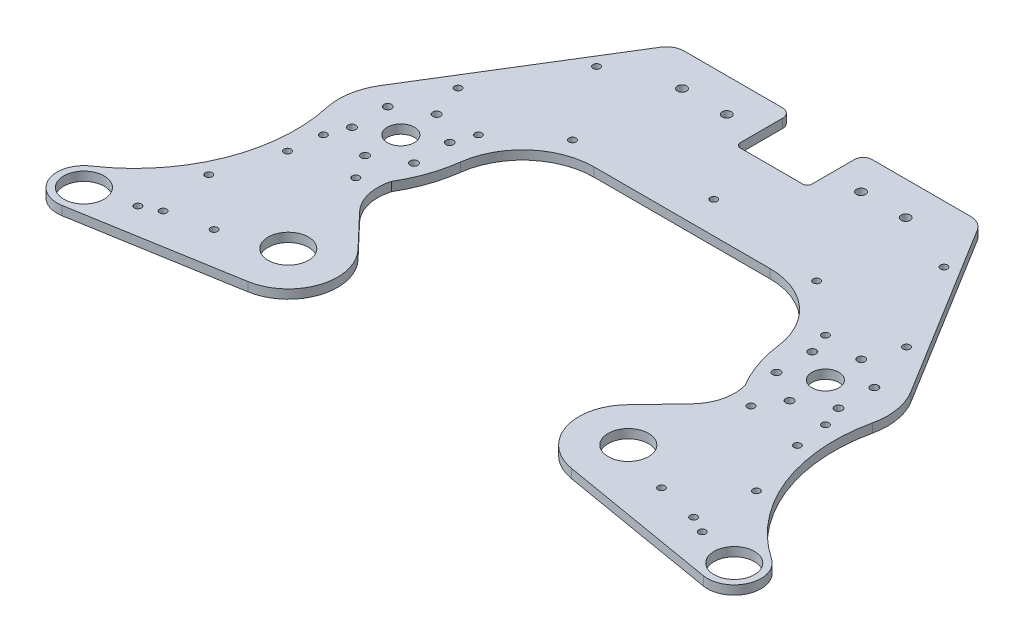
SolidWorks part; units mm, degrees
other "Marca1"
sketch "Croquis4" plane through (-508, 6.35, -221.5657) normal (0, 1, 0) x (1, 0, 0)
sketch "Croquis5" plane through (-262.5313, 6.35, -249.2375) normal (0, 1, 0) x (1, 0, 0)
sketch "Croquis6" plane through (-161.9393, 4.5, -121.1622) normal (0, 1, 0) x (1, 0, 0)
sketch "Croquis7" plane through (-262.5313, 6.35, -249.2375) normal (0, 1, 0) x (1, 0, 0)
sketch "Croquis9" plane through (-161.9393, 10.85, -121.1622) normal (0, 1, 0) x (1, 0, 0)
sketch "Croquis10" plane through (-262.5313, 6.35, -249.2375) normal (0, 1, 0) x (1, 0, 0)
sketch "Croquis12" plane through (-264.3199, 10.85, -20.8386) normal (0, 1, 0) x (1, 0, 0)
sketch "Croquis15" plane through (-262.5313, 6.35, -249.2375) normal (0, 1, 0) x (1, 0, 0)
sketch "Croquis16" plane through (-262.5313, 6.35, -249.2375) normal (0, 1, 0) x (1, 0, 0)
sketch "Croquis17" plane through (-262.5313, 6.35, -249.2375) normal (0, 1, 0) x (1, 0, 0)
sketch "Croquis18" plane through (-262.5313, 6.35, -249.2375) normal (0, 1, 0) x (1, 0, 0)
sketch "Croquis19" [suppressed] plane through (-264.3199, 10.85, -20.8386) normal (0, 1, 0) x (1, 0, 0)
sketch "Croquis20" [suppressed] plane through (-161.9393, 10.85, -121.1622) normal (0, 1, 0) x (1, 0, 0)
sketch "Croquis21" plane through (-264.3199, 10.85, -20.8386) normal (0, 1, 0) x (1, 0, 0)
sketch "Croquis22" plane through (-262.5313, 6.35, -249.2375) normal (0, 1, 0) x (1, 0, 0)
sketch "Croquis23" plane through (-262.5313, 6.35, -261.9375) normal (0, 1, 0) x (1, 0, 0)
sketch "Croquis24" plane through (-262.5313, 6.35, -261.9375) normal (0, 1, 0) x (1, 0, 0)
sketch "Croquis26" plane through (-262.5313, 7.9375, -34.9979) normal (0, 1, 0) x (1, 0, 0)
sketch "Croquis27" plane through (-262.5313, 6.35, -261.9375) normal (0, 1, 0) x (1, 0, 0)
sketch "Croquis28" plane through (-262.5313, 7.9375, -34.9979) normal (0, 1, 0) x (1, 0, 0)
sketch "Croquis29" plane through (-262.5313, 6.35, -261.9375) normal (0, 1, 0) x (1, 0, 0)
sketch "Croquis30" [suppressed] plane through (-262.5313, 7.9375, -34.9979) normal (0, 1, 0) x (1, 0, 0)
sketch "Croquis31" plane through (-262.5313, 7.9375, -34.9979) normal (0, 1, 0) x (1, 0, 0)
sketch "Croquis32" plane through (-161.9393, 10.85, -121.1622) normal (0, 1, 0) x (1, 0, 0)
material "Acrílico (Impacto medio-alto)"
ref_plane "Alzado" through (0, 0, 0) normal (0, 0, 1) x (1, 0, 0)
ref_plane "Planta" through (0, 0, 0) normal (0, 1, 0) x (1, 0, 0)
ref_plane "Vista lateral" through (0, 0, 0) normal (1, 0, 0) x (0, 0, -1)
sketch "Dibujo" plane through (0, 0, 0) normal (0, 1, 0) x (1, 0, 0)
  line L0 (0, 0) -> (0, 158.75) construction
  line L1 (0, 158.75) -> (-508, 158.75) construction
  line L2 (-126.4251, 18.2045) -> (-236.5182, -16.7205) construction
  line L3 (-224.9681, -53.1295) -> (-114.8749, -18.2045) construction
  line L4 (-160.1534, 108.938) -> (-149.1603, -2.8048) construction
  line L5 (-141.9901, 113.8973) -> (-94.6704, 12.0732) construction
  circle A0 centre (-120.65, 0) radius 50.8
  circle A1 centre (-230.7431, -34.925) radius 28.575
  arc A2 (-236.5182, -16.7205) -> (-224.9681, -53.1295) centre (-230.7431, -34.925) ccw construction
  arc A3 (-114.8749, -18.2045) -> (-126.4251, 18.2045) centre (-120.65, 0) ccw construction
  circle A4 centre (-150.65, 109.8729) radius 30
  arc A5 (-141.9901, 113.8973) -> (-160.1534, 108.938) centre (-150.65, 109.8729) ccw construction
  arc A6 (-149.1603, -2.8048) -> (-94.6704, 12.0732) centre (-120.65, 0) ccw construction
  dimension "D1" = 101.6
  dimension "D5" = 57.15
  dimension "D6" = 38.1972
  dimension "D9" = 60
  dimension "D10" = 19.0986
  dimension "D11" = 57.2958
  dimension "D2" = 241.3
  dimension "D3" = 508
  dimension "D4" = 107.95
  dimension "D8" = 34.925
  dimension "D13" = 241.3
sketch "Croquis2" plane through (0, 0, 0) normal (0, 1, 0) x (1, 0, 0)
  line L0 (-227.5452, -53.7047) -> (-114.7749, -34.5012)
  line L1 (-188.1793, 133.0118) -> (-112.4104, 255.9027)
  line L2 (-101.6, 261.9375) -> (101.6, 261.9375)
  line L3 (0, 287.155) -> (0, -59.1328) construction
  line L4 (188.1793, 133.0118) -> (112.4104, 255.9027)
  line L5 (227.5452, -53.7047) -> (114.7749, -34.5012)
  line L6 (-95.3203, 24.1508) -> (-117.9194, 47.853)
  line L7 (-141.9901, 113.8973) -> (-94.6704, 12.0732) construction
  line L8 (0, 158.75) -> (-508, 158.75) construction
  line L9 (-62.4132, 158.75) -> (62.4132, 158.75)
  line L10 (95.3203, 24.1508) -> (117.9194, 47.853)
  line L12 (0, 158.75) -> (0, -117.475) construction
  line L13 (-117.475, -117.475) -> (117.475, -117.475) construction
  line L14 (-117.475, -117.475) -> (-117.475, 117.475) construction
  line L15 (-117.475, 117.475) -> (117.475, 117.475) construction
  line L16 (117.475, -117.475) -> (117.475, 117.475) construction
  line L17 (-117.475, -117.475) -> (117.475, 117.475) construction
  line L18 (-117.475, 117.475) -> (117.475, -117.475) construction
  line L20 (-25.4381, 261.9375) -> (25.4381, 261.9375)
  line L21 (-25.4381, 261.9375) -> (-25.4381, 222.25)
  line L22 (-25.4381, 222.25) -> (25.4381, 222.25)
  line L23 (25.4381, 261.9375) -> (25.4381, 222.25)
  line L24 (-25.4381, 261.9375) -> (25.4381, 222.25) construction
  line L25 (-25.4381, 222.25) -> (25.4381, 261.9375) construction
  circle A0 centre (-230.7431, -34.925) radius 14.3256
  circle A1 centre (-120.65, 0) radius 14.3256
  circle A3 centre (-230.7431, -34.925) radius 19.05
  circle A4 centre (-120.65, 0) radius 34.9979
  arc A6 (-149.1603, -2.8048) -> (-94.6704, 12.0732) centre (-120.65, 0) ccw construction
  arc A7 (-193.697, 100.3433) -> (-241.3934, -19.1303) centre (-305.2952, 75.6382) cw
  arc A8 (-112.4104, 255.9027) -> (-101.6, 261.9375) centre (-101.6, 249.2375) cw
  arc A10 (-117.9194, 47.853) -> (-125.3591, 78.1101) centre (-95.246, 69.4712) cw
  arc A11 (112.4104, 255.9027) -> (101.6, 261.9375) centre (101.6, 249.2375) ccw
  arc A12 (193.697, 100.3433) -> (241.3934, -19.1303) centre (305.2952, 75.6382) ccw
  arc A13 (-112.7986, 114.4272) -> (-62.4132, 158.75) centre (-62.4132, 107.95) cw
  arc A14 (188.1793, 133.0118) -> (193.697, 100.3433) centre (150.65, 109.8729) cw
  circle A15 centre (120.65, 0) radius 34.9979
  circle A16 centre (230.7431, -34.925) radius 19.05
  circle A17 centre (150.65, 109.8729) radius 9.5631
  circle A18 centre (120.65, 0) radius 14.3256
  circle A19 centre (230.7431, -34.925) radius 14.3256
  circle A20 centre (-150.65, 109.8729) radius 25.4 construction
  circle A21 centre (-150.65, 135.2729) radius 2.75
  circle A22 centre (-128.653, 122.5729) radius 2.75
  circle A23 centre (-128.653, 97.1729) radius 2.75
  circle A24 centre (-150.65, 84.4729) radius 2.75
  circle A25 centre (-172.647, 97.1729) radius 2.75
  circle A26 centre (-172.647, 122.5729) radius 2.75
  circle A27 centre (150.65, 109.8729) radius 25.4 construction
  circle A28 centre (172.647, 122.5729) radius 2.75
  circle A29 centre (172.647, 97.1729) radius 2.75
  circle A30 centre (150.65, 84.4729) radius 2.75
  circle A31 centre (128.653, 97.1729) radius 2.75
  circle A32 centre (128.653, 122.5729) radius 2.75
  circle A33 centre (150.65, 135.2729) radius 2.75
  arc A35 (-188.1793, 133.0118) -> (-193.697, 100.3433) centre (-150.65, 109.8729) ccw
  arc A36 (112.7986, 114.4272) -> (62.4132, 158.75) centre (62.4132, 107.95) ccw
  arc A37 (125.3591, 78.1101) -> (112.7986, 114.4272) centre (206.3577, 126.4546) cw
  circle A39 centre (-150.65, 109.8729) radius 9.5631
  circle A40 centre (-120.65, 0) radius 50.8 construction
  circle A41 centre (-150.65, 109.8729) radius 36.35 construction
  arc A42 (117.9194, 47.853) -> (125.3591, 78.1101) centre (95.246, 69.4712) ccw
  circle A43 centre (-150.65, 109.8729) radius 30 construction
  arc A44 (-125.3591, 78.1101) -> (-112.7986, 114.4272) centre (-206.3577, 126.4546) ccw
  point P53 (0, 261.9375)
  point P71 (-150.65, 109.8729)
  point P88 (-117.2099, 95.6223)
  point P89 (150.65, 109.8729)
  point P93 (0, 158.75)
  point P97 (0, 0)
  point P104 (0, 242.0938)
  dimension "D1" = 28.6512
  dimension "D2" = 6.35
  dimension "D3" = 6.35
  dimension "D4" = 38.1
  dimension "D5" = 114.3
  dimension "D6" = 31.3278
  dimension "D7" = 32.7493
  dimension "D9" = 12.7
  dimension "D11" = 50.8
  dimension "D12" = 5.5
  dimension "D10" = 50.8
  dimension "D14" = 234.95
  dimension "D15" = 94.329
  dimension "D16" = 6.2059
  dimension "D17" = 34.4369
  dimension "D21" = 19.1262
  dimension "D8" = 203.2
  dimension "D18" = 50.8762
  dimension "D19" = 39.6875
  dimension "D20" = 63.5
  dimension "D13" = 6
extrude "Saliente-Extruir1" add sketch "Croquis2" along normal blind 6.35 contours A15 L5 A16 A12 A14 L4 A11 L2 A8 L1 A35 A7 A3 L0 A4 A32 A30 A28 A26 A25 A24 A23 A22 A21 A39 A17 A29 A31 A33 | A15 A18 | A16 A19 | A4 A1 | A3 A0 | L23 L2 L21 L22 | A39 | A25 | A26 | A22 | A23 | A24 | A21 | A17 | A33 | A32 | A28 | A31 | A30 | A29 region at (-211.7782, 0, 50.9334) region at (-247.9271, 0, 41.8078) region at (-152.9287, 0, -10.7066) region at (0, 0, -242.0938) region at (133.2892, 0, -31.5721) region at (247.0869, 0, 26.2333) region at (150.65, 0, -109.8729) region at (-150.65, 0, -135.2729) region at (-128.653, 0, -122.5729) region at (-128.653, 0, -97.1729) region at (-150.65, 0, -84.4729) region at (-172.647, 0, -97.1729) region at (-172.647, 0, -122.5729) region at (172.647, 0, -122.5729) region at (172.647, 0, -97.1729) region at (150.65, 0, -84.4729) region at (128.653, 0, -97.1729) region at (128.653, 0, -122.5729) region at (150.65, 0, -135.2729) region at (-150.65, 0, -109.8729)
extrude "Cortar-Extruir1" cut sketch "Croquis2<4>" along normal through all contours L23 L2 L21 L22 | A17 | A29 | A30 | A31 | A32 | A33 | A28 | A39 | A26 | A21 | A22 | A23 | A25 | A24 region at (0, 0, -242.0938) region at (150.65, 0, -109.8729) region at (-150.65, 0, -135.2729) region at (-128.653, 0, -122.5729) region at (-128.653, 0, -97.1729) region at (-150.65, 0, -84.4729) region at (-172.647, 0, -97.1729) region at (-172.647, 0, -122.5729) region at (172.647, 0, -122.5729) region at (172.647, 0, -97.1729) region at (150.65, 0, -84.4729) region at (128.653, 0, -97.1729) region at (128.653, 0, -122.5729) region at (150.65, 0, -135.2729) region at (-150.65, 0, -109.8729)
sketch "Croquis2<4>" plane through (0, 0, 0) normal (0, 1, 0) x (1, 0, 0) same geometry as "Croquis2"
sketch "Croquis14" plane through (0, 6.35, 0) normal (0, 1, 0) x (1, 0, 0)
  line L0 (-227.5452, -53.7047) -> (-114.7749, -34.5012) construction
  line L1 (-101.6, 261.9375) -> (-25.4381, 261.9375) construction
  line L2 (-25.4381, 261.9375) -> (-25.4381, 222.25) construction
  line L3 (-150.65, 109.8729) -> (-178.1494, 82.3735) construction
  line L4 (-150.65, 109.8729) -> (-150.65, 78.9066) construction
  line L5 (0, 158.75) -> (-508, 158.75) construction
  line L6 (-184.0813, 84.6396) -> (-171.4116, 117.8043)
  line L7 (-188.1793, 133.0118) -> (-112.4104, 255.9027) construction
  line L8 (-175.8833, 76.4416) -> (-142.7186, 89.1113)
  line L9 (-62.4132, 158.75) -> (62.4132, 158.75) construction
  line L10 (-150.65, 109.8729) -> (-164.4835, 123.7064) construction
  line L11 (25.4381, 261.9375) -> (25.4381, 222.25) construction
  line L12 (0, 0) -> (0, 222.25) construction
  line L13 (-25.4381, 222.25) -> (25.4381, 222.25) construction
  line L14 (-117.2187, 135.1062) -> (-129.8884, 101.9415)
  line L15 (-125.4167, 143.3042) -> (-158.5814, 130.6345)
  line L16 (0, 263.811) -> (0, 117.8043) construction
  line L17 (-135.7241, 31.5852) -> (-238.9692, -17.6887) construction
  circle A0 centre (-188.1981, -21.2387) radius 4.7625
  circle A1 centre (-188.1981, -21.2387) radius 2.4892
  circle A2 centre (-230.7431, -34.925) radius 28.575 construction
  circle A5 centre (-194.31, 17.2379) radius 4.7625
  circle A6 centre (-194.31, 17.2379) radius 2.4892
  circle A7 centre (-180.9008, 59.69) radius 4.7625
  circle A8 centre (-180.9008, 59.69) radius 2.4892
  arc A9 (-241.3934, -19.1303) -> (-193.697, 100.3433) centre (-305.2952, 75.6382) ccw construction
  circle A10 centre (-47.625, 238.125) radius 4.7625
  circle A11 centre (-47.625, 238.125) radius 3.2639
  circle A12 centre (-79.375, 238.125) radius 4.7625
  circle A13 centre (-79.375, 238.125) radius 3.2639
  circle A14 centre (-120.65, 0) radius 50.8 construction
  circle A15 centre (-140.2263, 67.4904) radius 4.7625
  circle A16 centre (-140.2263, 67.4904) radius 2.4892
  circle A17 centre (47.625, 238.125) radius 3.2639
  circle A18 centre (47.625, 238.125) radius 4.7625
  arc A19 (-125.3591, 78.1101) -> (-117.9194, 47.853) centre (-95.246, 69.4712) ccw construction
  circle A20 centre (79.375, 238.125) radius 3.2639
  circle A21 centre (-150.65, 109.8729) radius 30 construction
  circle A22 centre (0, 181.2925) radius 4.7625
  circle A23 centre (0, 181.2925) radius 2.4892
  circle A24 centre (-86.6348, 167.64) radius 4.7625
  circle A25 centre (-86.6348, 167.64) radius 2.4892
  circle A26 centre (-159.1395, 158.938) radius 4.7625
  circle A27 centre (-159.1395, 158.938) radius 2.4892
  circle A28 centre (188.1981, -21.2387) radius 2.4892
  circle A29 centre (188.1981, -21.2387) radius 4.7625
  circle A30 centre (194.31, 17.2379) radius 2.4892
  circle A31 centre (194.31, 17.2379) radius 4.7625
  circle A32 centre (180.9008, 59.69) radius 2.4892
  circle A33 centre (180.9008, 59.69) radius 4.7625
  circle A34 centre (140.2263, 67.4904) radius 2.4892
  circle A35 centre (140.2263, 67.4904) radius 4.7625
  circle A36 centre (86.6348, 167.64) radius 2.4892
  circle A37 centre (86.6348, 167.64) radius 4.7625
  circle A38 centre (159.1395, 158.938) radius 2.4892
  circle A39 centre (159.1395, 158.938) radius 4.7625
  circle A40 centre (79.375, 238.125) radius 4.7625
  circle A41 centre (-178.1494, 82.3735) radius 6.35
  circle A42 centre (-178.1494, 82.3735) radius 2.4892
  circle A45 centre (-150.65, 109.8729) radius 30 construction
  circle A46 centre (-150.65, 109.8729) radius 22.225
  circle A47 centre (-123.1506, 137.3723) radius 2.4892
  circle A48 centre (-123.1506, 137.3723) radius 6.35
  circle A49 centre (-123.2693, 221.3514) radius 4.7625
  circle A50 centre (-123.2693, 221.3514) radius 2.4892
  circle A51 centre (178.1494, 82.3735) radius 6.35
  circle A52 centre (178.1494, 82.3735) radius 2.4892
  circle A53 centre (123.1506, 137.3723) radius 6.35
  circle A54 centre (123.1506, 137.3723) radius 2.4892
  circle A55 centre (123.2693, 221.3514) radius 2.4892
  circle A56 centre (123.2693, 221.3514) radius 4.7625
  circle A57 centre (-200.2631, -27.1581) radius 4.7625
  circle A58 centre (-200.2631, -27.1581) radius 2.4892
  circle A59 centre (-158.75, -14.5845) radius 4.7625
  circle A60 centre (-158.75, -14.5845) radius 2.4892
  circle A61 centre (-120.65, 0) radius 14.3256 construction
  circle A62 centre (-120.65, 0) radius 34.9979 construction
  arc A63 (-114.7749, -34.5012) -> (-95.3203, 24.1508) centre (-120.65, 0) ccw construction
  arc A64 (-236.5182, -16.7205) -> (-224.9681, -53.1295) centre (-230.7431, -34.925) ccw construction
  circle A65 centre (-230.7431, -34.925) radius 14.3256 construction
  circle A66 centre (158.75, -14.5845) radius 4.7625
  circle A67 centre (158.75, -14.5845) radius 2.4892
  circle A68 centre (200.2631, -27.1581) radius 4.7625
  circle A69 centre (200.2631, -27.1581) radius 2.4892
  dimension "D1" = 9.525
  dimension "D2" = 4.9784
  dimension "D3" = 25.4
  dimension "D4" = 42.545
  dimension "D5" = 6.35
  dimension "D6" = 6.35
  dimension "D7" = 8.89
  dimension "D8" = 73.66
  dimension "D9" = 8.89
  dimension "D10" = 7.62
  dimension "D11" = 8.89
  dimension "D12" = 63.5
  dimension "D13" = 17.78
  dimension "D14" = 20.6756
  dimension "D15" = 63.5
  dimension "D16" = 6.35
  dimension "D17" = 23.8125
  dimension "D18" = 22.1869
  dimension "D19" = 31.75
  dimension "D20" = 45
  dimension "D21" = 12.7
  dimension "D22" = 60
  dimension "D23" = 2.54
  dimension "D24" = 44.45
  dimension "D26" = 6.5278
  dimension "D27" = 8.89
  dimension "D28" = 46.99
  dimension "D29" = 38.1
  dimension "D30" = 31.75
  dimension "D31" = 30.48
  dimension "D32" = 21.59
  dimension "D25" = 90
extrude "Cortar-Extruir2" cut sketch "Croquis14" against normal through all contours A1 | A6 | A8 | A16 | A27 | A25 | A23 L12 | L12 A23 | A36 | A38 | A34 | A32 | A30 | A28 | A13 | A11 | A17 | A20 | A55 | A54 | A52 | A47 | A50 | A42 | A60 | A58 | A67 | A69 region at (-188.1981, 6.35, 21.2387) region at (-194.31, 6.35, -17.2379) region at (-180.9008, 6.35, -59.69) region at (-47.625, 6.35, -238.125) region at (-79.375, 6.35, -238.125) region at (-140.2263, 6.35, -67.4904) region at (47.625, 6.35, -238.125) region at (79.375, 6.35, -238.125) region at (0, 6.35, -181.2925) region at (-86.6348, 6.35, -167.64) region at (-159.1395, 6.35, -158.938) region at (188.1981, 6.35, 21.2387) region at (194.31, 6.35, -17.2379) region at (180.9008, 6.35, -59.69) region at (140.2263, 6.35, -67.4904) region at (86.6348, 6.35, -167.64) region at (159.1395, 6.35, -158.938) region at (-178.1494, 6.35, -82.3735) region at (-123.1506, 6.35, -137.3723) region at (-123.2693, 6.35, -221.3514) region at (178.1494, 6.35, -82.3735) region at (123.1506, 6.35, -137.3723) region at (123.2693, 6.35, -221.3514) region at (-200.2631, 6.35, 27.1581) region at (-158.75, 6.35, 14.5845) region at (158.75, 6.35, 14.5845) region at (200.2631, 6.35, 27.1581)
fillet "Redondeo1" radius 6.35 2 edges at (25.4381, 3.175, -261.9375) (-25.4381, 3.175, -261.9375)
fillet "Redondeo2" radius 3.175 2 edges at (-25.4381, 3.175, -222.25) (25.4381, 3.175, -222.25)
sketch "Croquis8" [suppressed] plane through (0, 6.35, 0) normal (0, 1, 0) x (1, 0, 0)
  line L0 (-141.9901, 113.8973) -> (-94.6704, 12.0732) construction
  line L1 (-160.1534, 108.938) -> (-149.1603, -2.8048) construction
  line L2 (-141.9901, 113.8973) -> (-94.6704, 12.0732) construction
  line L3 (-160.1534, 108.938) -> (-149.1603, -2.8048) construction
  line L4 (-158.1033, 109.1397) -> (-147.1102, -2.6031)
  line L5 (-143.8583, 113.0292) -> (-96.5386, 11.2051)
  line L6 (-161.8851, 108.7676) -> (-150.8919, -2.9752)
  line L7 (-140.4122, 114.6306) -> (-93.0925, 12.8065)
  arc A0 (-141.9901, 113.8973) -> (-160.1534, 108.938) centre (-150.65, 109.8729) ccw construction
  arc A1 (-149.1603, -2.8048) -> (-94.6704, 12.0732) centre (-120.65, 0) ccw construction
  arc A2 (-141.9901, 113.8973) -> (-160.1534, 108.938) centre (-150.65, 109.8729) ccw construction
  arc A3 (-149.1603, -2.8048) -> (-94.6704, 12.0732) centre (-120.65, 0) ccw construction
  arc A4 (-147.1102, -2.6031) -> (-96.5386, 11.2051) centre (-120.65, 0) ccw
  arc A5 (-143.8583, 113.0292) -> (-158.1033, 109.1397) centre (-150.65, 109.8729) ccw
  arc A6 (-150.8919, -2.9752) -> (-93.0925, 12.8065) centre (-120.65, 0) ccw
  arc A7 (-140.4122, 114.6306) -> (-161.8851, 108.7676) centre (-150.65, 109.8729) ccw
  dimension "D1" = 2.06
  dimension "D2" = 3.8
extrude "Saliente-Extruir2" [suppressed] add sketch "Croquis8" along normal mid plane 9 separate body
delete or keep bodies "Sólido-Eliminar/Conservar 1" [suppressed] type delete bodies bodies 106
sketch "Croquis11" [suppressed] plane through (0, 6.35, 0) normal (0, 1, 0) x (1, 0, 0)
  line L0 (-238.258, -53.2954) -> (-115.4267, -18.3704) construction
  line L1 (-125.8733, 18.3704) -> (-248.7046, -16.5546) construction
  line L2 (-238.258, -53.2954) -> (-115.4267, -18.3704) construction
  line L3 (-125.8733, 18.3704) -> (-248.7046, -16.5546) construction
  line L4 (-125.3099, 16.389) -> (-248.1413, -18.536)
  line L5 (-238.8214, -51.314) -> (-115.9901, -16.389)
  line L6 (-126.3492, 20.0441) -> (-249.1805, -14.8809)
  line L7 (-237.7821, -54.9691) -> (-114.9508, -20.0441)
  arc A0 (-115.4267, -18.3704) -> (-125.8733, 18.3704) centre (-120.65, 0) ccw construction
  arc A1 (-248.7046, -16.5546) -> (-238.258, -53.2954) centre (-243.4813, -34.925) ccw construction
  arc A2 (-115.4267, -18.3704) -> (-125.8733, 18.3704) centre (-120.65, 0) ccw construction
  arc A3 (-248.7046, -16.5546) -> (-238.258, -53.2954) centre (-243.4813, -34.925) ccw construction
  arc A4 (-248.1413, -18.536) -> (-238.8214, -51.314) centre (-243.4813, -34.925) ccw
  arc A5 (-115.9901, -16.389) -> (-125.3099, 16.389) centre (-120.65, 0) ccw
  arc A6 (-249.1805, -14.8809) -> (-237.7821, -54.9691) centre (-243.4813, -34.925) ccw
  arc A7 (-114.9508, -20.0441) -> (-126.3492, 20.0441) centre (-120.65, 0) ccw
  dimension "D1" = 2.06
  dimension "D2" = 3.8
extrude "Saliente-Extruir3" [suppressed] add sketch "Croquis11" along normal mid plane 9 separate body
delete or keep bodies "Sólido-Eliminar/Conservar 2" [suppressed] type delete bodies bodies 106
sketch "Croquis25" [suppressed] plane through (0, 6.35, 0) normal (0, 1, 0) x (1, 0, 0)
  line L0 (-115.3574, -34.5954) -> (-240.6004, -53.7559)
  line L1 (-134.3508, 32.2047) -> (-250.9389, -17.3954)
  arc A0 (-115.3574, -34.5954) -> (-134.3508, 32.2047) centre (-120.65, 0) ccw
  arc A1 (-250.9389, -17.3954) -> (-240.6004, -53.7559) centre (-243.4813, -34.925) ccw
  arc A2 (-251.6976, -17.7379) -> (-240.6004, -53.7559) centre (-243.4813, -34.925) ccw construction
  arc A3 (-115.3574, -34.5954) -> (-95.3203, 24.1508) centre (-120.65, 0) ccw construction
  circle A4 centre (-158.75, -12.6793) radius 4.7625
  circle A5 centre (-158.75, -12.6793) radius 2.4892
  circle A8 centre (-120.65, 0) radius 14.3256 construction
  circle A9 centre (-213.0013, -27.6924) radius 4.7625
  circle A10 centre (-213.0013, -27.6924) radius 2.4892
  circle A11 centre (-243.4813, -34.925) radius 14.3256 construction
  circle A12 centre (-120.65, 0) radius 14.3256
  circle A13 centre (-243.4813, -34.925) radius 14.3256
  dimension "D1" = 4.9784
  dimension "D2" = 9.525
  dimension "D3" = 38.1
  dimension "D4" = 31.75
  dimension "D5" = 30.48
  dimension "D6" = 21.59
extrude "Saliente-Extruir4" [suppressed] add sketch "Croquis25" along normal blind 1.5875 separate body contours L1 A1 L0 A0 A13 A12 A9 A4 | A9 A10 | A4 A5
delete or keep bodies "Sólido-Eliminar/Conservar 3" [suppressed] type keep bodies bodies 112
equation "\"D7@Dibujo\"=( 70 * 5mm )  + 1mm"
equation "\"D10@Dibujo\" = 12 * 5mm / pi"
equation "\"D11@Dibujo\" = 36 * 5mm / pi"
equation "\"D12@Dibujo\" =  ( 70 * 5mm )  + 1mm"
